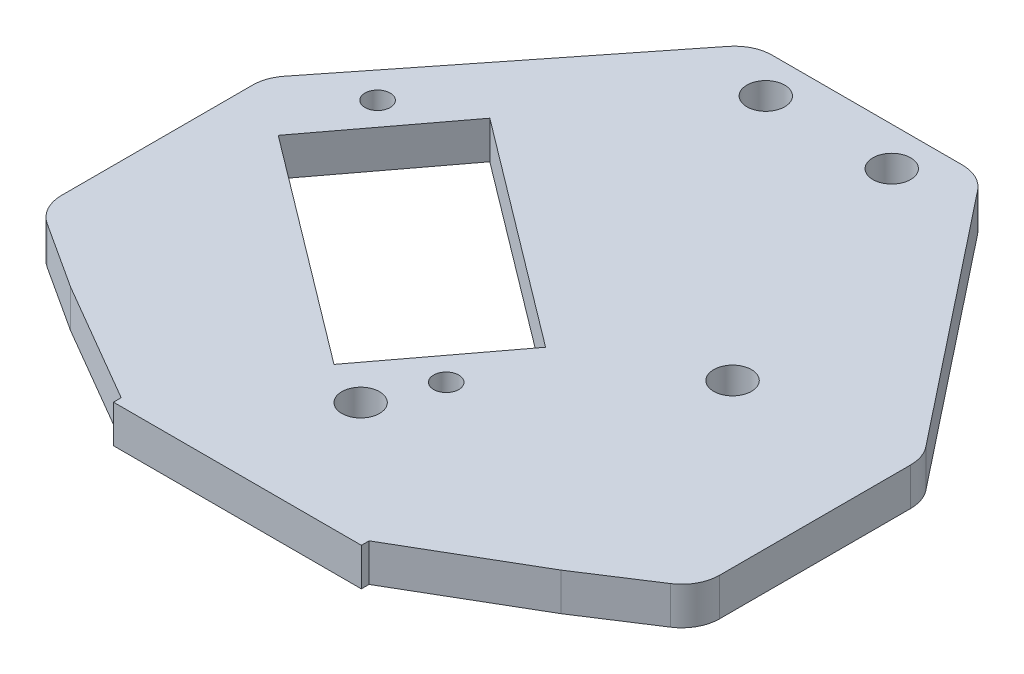
SolidWorks part; units mm, degrees
ref_plane "Front Plane" through (0, 0, 0) normal (0, 0, 1) x (1, 0, 0)
ref_plane "Top Plane" through (0, 0, 0) normal (0, 1, 0) x (1, 0, 0)
ref_plane "Right Plane" through (0, 0, 0) normal (1, 0, 0) x (0, 0, -1)
sketch "Sketch1" plane through (0, 0, 0) normal (0, 1, 0) x (1, 0, 0)
  line L7 (-4.1595, 37.5951) -> (4.1595, 37.5951)
  line L8 (-9.9025, 36.4566) -> (-20.3157, 23.2959) construction
  line L10 (0, 0) -> (0, -15.9475) construction
  line L12 (-9.9025, 36.4566) -> (-20.3157, 23.2959)
  line L15 (-20.9631, 21.4344) -> (-20.9631, -5.9026) construction
  line L16 (-19.4729, -6.2109) -> (-9.8452, -11.8182)
  line L19 (-9.8452, -11.8182) -> (-9.8452, -21.8182)
  line L21 (0, 43.4367) -> (0, 47.8638) construction
  line L22 (-9.8452, -21.8182) -> (-6.8452, -21.8182)
  line L23 (-6.8452, -21.8182) -> (-6.8452, -12.4305)
  line L24 (-6.8452, -12.4305) -> (6.8452, -12.4305)
  line L25 (-4.1595, 37.5951) -> (-7.5499, 37.5951)
  line L28 (24.762, -2.7815) -> (19.4729, -6.2109)
  line L29 (26.1299, 14.9044) -> (26.1299, -0.2643)
  line L30 (18.8536, 25.1438) -> (25.4825, 16.7659)
  line L31 (-18.8536, 25.1438) -> (-25.4825, 16.7659)
  line L32 (-26.1299, 14.9044) -> (-26.1299, -0.2643)
  line L33 (-24.762, -2.7815) -> (-19.4729, -6.2109)
  line L34 (4.1595, 37.5951) -> (7.5499, 37.5951)
  line L35 (6.8452, -21.8182) -> (6.8452, -12.4305)
  line L36 (9.8452, -21.8182) -> (6.8452, -21.8182)
  line L37 (9.8452, -11.8182) -> (9.8452, -21.8182)
  line L38 (19.4729, -6.2109) -> (9.8452, -11.8182)
  line L39 (0, 0) -> (0, 37.5951) construction
  line L42 (9.9025, 36.4566) -> (20.3157, 23.2959)
  arc A1 (-7.5499, 37.5951) -> (-9.9025, 36.4566) centre (-7.5499, 34.5951) ccw construction
  circle A4 centre (-5.0017, 34.5359) radius 1.5 construction
  circle A8 centre (-5.0017, 34.5359) radius 1.5
  arc A11 (-7.5499, 37.5951) -> (-9.9025, 36.4566) centre (-7.5499, 34.5951) ccw
  arc A12 (-19.7137, -6.0547) -> (-19.4729, -6.2109) centre (-17.9631, -3.6185) ccw
  arc A14 (25.4825, 16.7659) -> (26.1299, 14.9044) centre (23.1299, 14.9044) cw
  arc A15 (26.1299, -0.2643) -> (24.762, -2.7815) centre (23.1299, -0.2643) cw
  arc A16 (19.7137, -6.0547) -> (19.4729, -6.2109) centre (17.9631, -3.6185) cw
  arc A17 (-26.1299, -0.2643) -> (-24.762, -2.7815) centre (-23.1299, -0.2643) ccw
  arc A18 (-25.4825, 16.7659) -> (-26.1299, 14.9044) centre (-23.1299, 14.9044) ccw
  arc A19 (7.5499, 37.5951) -> (9.9025, 36.4566) centre (7.5499, 34.5951) cw
  circle A20 centre (5.0017, 34.5359) radius 1.5
  point P28 (0.1548, -12.4305)
  point P33 (-20.9631, -5.343)
  point P37 (0, -12.4305)
  point P41 (0.1548, -12.4305)
  point P46 (26.1299, 15.9477)
  point P48 (26.1299, -1.8946)
  point P49 (-0.1548, -12.4305)
  point P50 (20.9631, -5.343)
  point P54 (-26.1299, -1.8946)
  point P57 (-26.1299, 15.9477)
  dimension "D1" = 3
  dimension "D3" = 3
  dimension "D4" = 10
extrude "Boss-Extrude2" add sketch "Sketch1" along normal blind 3 contours A11 L12 A12 L16 L19 L22 L23 A8 region at (0, 0, -10.32)
mirror "Mirror1" about plane through (0, 0, 0) normal (1, 0, 0) of "Boss-Extrude2"
sketch "Sketch3" plane through (9.8452, 0, 0) normal (1, 0, 0) x (0, 0, -1)
  line L0 (0, 0) -> (-5.4214, -2.0662)
  line L1 (-10.362, -2.9757) -> (-38.362, -2.9757)
  line L2 (-46.7647, 6.1171) -> (-46.7647, 8.8248)
  line L3 (-36.7549, 18.9944) -> (-26.7549, 18.9944)
  line L4 (-14.3131, 13.6377) -> (-3.6185, 3)
  line L5 (-3.6185, 3) -> (0, 0)
  line L6 (-11.8182, 3) -> (-11.8182, 0) construction
  arc A0 (-5.4214, -2.0662) -> (-10.362, -2.9757) centre (-10.362, 10.8976) cw
  arc A1 (-38.362, -2.9757) -> (-43.5481, -1.0139) centre (-38.362, 4.8597) cw
  arc A2 (-43.5481, -1.0139) -> (-46.7647, 6.1171) centre (-37.2518, 6.1171) cw
  circle A5 centre (-29.5682, 8.0684) radius 5 construction
  arc A7 (-26.7549, 18.9944) -> (-14.3131, 13.6377) centre (-26.7549, 1.8671) cw
  arc A8 (-36.7549, 18.9944) -> (-46.7647, 8.8248) centre (-36.4897, 8.7223) ccw
  dimension "D1" = 10
  dimension "D2" = 17.75
  dimension "D3" = 28
  dimension "D4" = 10
extrude "Boss-Extrude3" add sketch "Sketch3" against normal blind 3
sketch "Sketch4" plane through (9.8452, 0, 0) normal (1, 0, 0) x (0, 0, -1)
  circle A0 centre (-29.5682, 8.0684) radius 5
mirror "Mirror2" about plane through (0, 0, 0) normal (1, 0, 0) of "Boss-Extrude3"
extrude "Cut-Extrude1" cut sketch "Sketch4" against normal up to surface (3 mm away) rebuild error yes
sketch "Sketch5" plane through (-9.8452, 0, 0) normal (-1, 0, 0) x (0, 0, 1)
  line L0 (14.3482, 8.0684) -> (44.7882, 8.0684) construction
  line L1 (14.3482, 8.5684) -> (44.7882, 8.5684)
  line L2 (14.3482, 7.5684) -> (44.7882, 7.5684)
  line L3 (29.5682, 1.2134) -> (29.5682, 14.9234) construction
  line L4 (29.0682, 1.2134) -> (29.0682, 14.9234)
  line L5 (30.0682, 1.2134) -> (30.0682, 14.9234)
  circle A0 centre (29.5682, 8.0684) radius 5 construction
  circle A1 centre (29.5682, 8.0684) radius 5 construction
  arc A2 (14.3482, 8.5684) -> (14.3482, 7.5684) centre (14.3482, 8.0684) ccw
  arc A3 (44.7882, 7.5684) -> (44.7882, 8.5684) centre (44.7882, 8.0684) ccw
  arc A4 (29.0682, 1.2134) -> (30.0682, 1.2134) centre (29.5682, 1.2134) ccw
  arc A5 (30.0682, 14.9234) -> (29.0682, 14.9234) centre (29.5682, 14.9234) ccw
  circle A6 centre (29.5682, 8.0684) radius 3.5
  point P5 (29.5682, 8.0684)
  point P11 (29.5682, 8.0684)
  dimension "D1" = 0.5
  dimension "D2" = 0.5
  dimension "D5" = 10
  dimension "D6" = 7
  dimension "D3" = 30.44
  dimension "D4" = 13.71
extrude "Cut-Extrude2" cut sketch "Sketch5" against normal blind 3 contours L5 A6 L2 | L2 A6 L4 | L4 A6 L1 | L1 A6 L5 | L2 A3 L1 A2 | L5 A4 L4 A5 region at (-9.8452, 9.7725, 27.8641) region at (-9.8452, 6.3644, 27.8641) region at (-9.8452, 9.7725, 31.2723) region at (-9.8452, 6.3644, 31.2723)
sketch "Sketch7" plane through (0, 3, 0) normal (0, 1, 0) x (1, 0, 0)
  line L0 (-14.4326, 22.0478) -> (3.5367, 8.507)
  line L1 (3.5367, 8.507) -> (-3.6851, -1.0766)
  line L2 (-3.6851, -1.0766) -> (-21.6544, 12.4642)
  line L3 (-21.6544, 12.4642) -> (-14.4326, 22.0478)
  line L26 (-6.8452, -3.6185) -> (-6.8452, -12.4305)
  line L27 (-6.8452, -3.6185) -> (-6.8452, -12.4305)
  line L42 (6.8452, -3.6185) -> (9.8452, -3.6185)
  line L43 (6.8452, -3.6185) -> (9.8452, -3.6185)
  line L44 (-9.9025, 36.4566) -> (-25.4825, 16.7659)
  line L45 (-9.9025, 36.4566) -> (-25.4825, 16.7659)
  line L46 (-19.4729, -6.2109) -> (-9.8452, -11.8182)
  line L47 (-19.4729, -6.2109) -> (-9.8452, -11.8182)
  line L48 (-9.8452, -11.8182) -> (-9.8452, -3.6185)
  line L50 (-9.8452, -11.8182) -> (-9.8452, -3.6185)
  line L52 (-24.762, -2.7815) -> (-19.4729, -6.2109)
  line L53 (-24.762, -2.7815) -> (-19.4729, -6.2109)
  line L54 (-9.8452, -3.6185) -> (-6.8452, -3.6185)
  line L55 (-9.8452, -3.6185) -> (-6.8452, -3.6185)
  line L56 (-26.1299, 14.9044) -> (-26.1299, -0.2643)
  line L57 (-26.1299, 14.9044) -> (-26.1299, -0.2643)
  line L62 (7.5499, 37.5951) -> (-7.5499, 37.5951)
  line L64 (7.5499, 37.5951) -> (-7.5499, 37.5951)
  line L66 (-6.8452, -12.4305) -> (6.8452, -12.4305)
  line L68 (-6.8452, -12.4305) -> (6.8452, -12.4305)
  line L70 (6.8452, -12.4305) -> (6.8452, -3.6185)
  line L72 (6.8452, -12.4305) -> (6.8452, -3.6185)
  line L74 (9.8452, -3.6185) -> (9.8452, -11.8182)
  line L76 (9.8452, -3.6185) -> (9.8452, -11.8182)
  line L78 (9.8452, -11.8182) -> (19.4729, -6.2109)
  line L80 (9.8452, -11.8182) -> (19.4729, -6.2109)
  line L82 (19.4729, -6.2109) -> (24.762, -2.7815)
  line L83 (19.4729, -6.2109) -> (24.762, -2.7815)
  line L84 (26.1299, -0.2643) -> (26.1299, 14.9044)
  line L85 (26.1299, -0.2643) -> (26.1299, 14.9044)
  line L86 (25.4825, 16.7659) -> (9.9025, 36.4566)
  line L87 (25.4825, 16.7659) -> (9.9025, 36.4566)
  circle A0 centre (-20.1199, 18.8207) radius 1
  circle A1 centre (2.0023, 2.1505) radius 1
  arc A3 (-7.5499, 37.5951) -> (-9.9025, 36.4566) centre (-7.5499, 34.5951) ccw
  arc A18 (-7.5499, 37.5951) -> (-9.9025, 36.4566) centre (-7.5499, 34.5951) ccw
  arc A19 (-25.4825, 16.7659) -> (-26.1299, 14.9044) centre (-23.1299, 14.9044) ccw
  arc A20 (-25.4825, 16.7659) -> (-26.1299, 14.9044) centre (-23.1299, 14.9044) ccw
  arc A22 (-26.1299, -0.2643) -> (-24.762, -2.7815) centre (-23.1299, -0.2643) ccw
  arc A24 (-26.1299, -0.2643) -> (-24.762, -2.7815) centre (-23.1299, -0.2643) ccw
  arc A25 (24.762, -2.7815) -> (26.1299, -0.2643) centre (23.1299, -0.2643) ccw
  arc A26 (24.762, -2.7815) -> (26.1299, -0.2643) centre (23.1299, -0.2643) ccw
  arc A27 (26.1299, 14.9044) -> (25.4825, 16.7659) centre (23.1299, 14.9044) ccw
  arc A28 (26.1299, 14.9044) -> (25.4825, 16.7659) centre (23.1299, 14.9044) ccw
  arc A29 (9.9025, 36.4566) -> (7.5499, 37.5951) centre (7.5499, 34.5951) ccw
  arc A30 (9.9025, 36.4566) -> (7.5499, 37.5951) centre (7.5499, 34.5951) ccw
  dimension "D2" = 12
  dimension "D3" = 22.5
  dimension "D1" = 0
sketch "Sketch8" plane through (0, 3, 0) normal (0, 1, 0) x (1, 0, 0)
  line L0 (-14.4326, 22.0478) -> (3.5367, 8.507) construction
  line L1 (3.5367, 8.507) -> (-3.6851, -1.0766) construction
  line L2 (-3.6851, -1.0766) -> (-21.6544, 12.4642) construction
  line L3 (-21.6544, 12.4642) -> (-14.4326, 22.0478) construction
  line L4 (-14.4326, 22.0478) -> (3.5367, 8.507)
  line L5 (3.5367, 8.507) -> (-3.6851, -1.0766)
  line L6 (-3.6851, -1.0766) -> (-21.6544, 12.4642)
  line L7 (-21.6544, 12.4642) -> (-14.4326, 22.0478)
  line L28 (-24.762, -2.7815) -> (-19.4729, -6.2109)
  line L30 (-6.8452, -3.6185) -> (-6.8452, -12.4305)
  line L31 (-6.8452, -3.6185) -> (-6.8452, -12.4305)
  line L44 (-24.762, -2.7815) -> (-19.4729, -6.2109)
  line L48 (6.8452, -3.6185) -> (9.8452, -3.6185)
  line L49 (6.8452, -3.6185) -> (9.8452, -3.6185)
  line L50 (-9.9025, 36.4566) -> (-25.4825, 16.7659)
  line L51 (-9.9025, 36.4566) -> (-25.4825, 16.7659)
  line L52 (-26.1299, 14.9044) -> (-26.1299, -0.2643)
  line L53 (-26.1299, 14.9044) -> (-26.1299, -0.2643)
  line L54 (-19.4729, -6.2109) -> (-9.8452, -11.8182)
  line L55 (-19.4729, -6.2109) -> (-9.8452, -11.8182)
  line L56 (-9.8452, -11.8182) -> (-9.8452, -3.6185)
  line L57 (-9.8452, -11.8182) -> (-9.8452, -3.6185)
  line L58 (-9.8452, -3.6185) -> (-6.8452, -3.6185)
  line L59 (-9.8452, -3.6185) -> (-6.8452, -3.6185)
  line L64 (7.5499, 37.5951) -> (-7.5499, 37.5951)
  line L66 (7.5499, 37.5951) -> (-7.5499, 37.5951)
  line L68 (-6.8452, -12.4305) -> (6.8452, -12.4305)
  line L70 (-6.8452, -12.4305) -> (6.8452, -12.4305)
  line L72 (6.8452, -12.4305) -> (6.8452, -3.6185)
  line L74 (6.8452, -12.4305) -> (6.8452, -3.6185)
  line L76 (9.8452, -3.6185) -> (9.8452, -11.8182)
  line L78 (9.8452, -3.6185) -> (9.8452, -11.8182)
  line L80 (9.8452, -11.8182) -> (19.4729, -6.2109)
  line L82 (9.8452, -11.8182) -> (19.4729, -6.2109)
  line L84 (19.4729, -6.2109) -> (24.762, -2.7815)
  line L85 (19.4729, -6.2109) -> (24.762, -2.7815)
  line L86 (26.1299, -0.2643) -> (26.1299, 14.9044)
  line L87 (26.1299, -0.2643) -> (26.1299, 14.9044)
  line L88 (25.4825, 16.7659) -> (9.9025, 36.4566)
  line L89 (25.4825, 16.7659) -> (9.9025, 36.4566)
  circle A0 centre (-20.1199, 18.8207) radius 1 construction
  circle A1 centre (2.0023, 2.1505) radius 1 construction
  circle A2 centre (-20.1199, 18.8207) radius 1
  circle A3 centre (2.0023, 2.1505) radius 1
  arc A5 (-7.5499, 37.5951) -> (-9.9025, 36.4566) centre (-7.5499, 34.5951) ccw
  arc A18 (-7.5499, 37.5951) -> (-9.9025, 36.4566) centre (-7.5499, 34.5951) ccw
  arc A19 (-25.4825, 16.7659) -> (-26.1299, 14.9044) centre (-23.1299, 14.9044) ccw
  arc A20 (-25.4825, 16.7659) -> (-26.1299, 14.9044) centre (-23.1299, 14.9044) ccw
  arc A21 (-26.1299, -0.2643) -> (-24.762, -2.7815) centre (-23.1299, -0.2643) ccw
  arc A22 (-26.1299, -0.2643) -> (-24.762, -2.7815) centre (-23.1299, -0.2643) ccw
  arc A23 (24.762, -2.7815) -> (26.1299, -0.2643) centre (23.1299, -0.2643) ccw
  arc A24 (24.762, -2.7815) -> (26.1299, -0.2643) centre (23.1299, -0.2643) ccw
  arc A25 (26.1299, 14.9044) -> (25.4825, 16.7659) centre (23.1299, 14.9044) ccw
  arc A26 (26.1299, 14.9044) -> (25.4825, 16.7659) centre (23.1299, 14.9044) ccw
  arc A27 (9.9025, 36.4566) -> (7.5499, 37.5951) centre (7.5499, 34.5951) ccw
  arc A28 (9.9025, 36.4566) -> (7.5499, 37.5951) centre (7.5499, 34.5951) ccw
  dimension "D1" = 0
sketch "Sketch9" plane through (0, 3, 0) normal (0, 1, 0) x (1, 0, 0)
  line L0 (3.5367, 8.507) -> (-3.6851, -1.0766) construction
  line L1 (-14.4326, 22.0478) -> (3.5367, 8.507) construction
  line L2 (-3.6851, -1.0766) -> (-21.6544, 12.4642) construction
  line L3 (-21.6544, 12.4642) -> (-14.4326, 22.0478) construction
  line L4 (3.5367, 8.507) -> (-3.6851, -1.0766)
  line L5 (-14.4326, 22.0478) -> (3.5367, 8.507)
  line L6 (-3.6851, -1.0766) -> (-21.6544, 12.4642)
  line L7 (-21.6544, 12.4642) -> (-14.4326, 22.0478)
  line L28 (-24.762, -2.7815) -> (-19.4729, -6.2109)
  line L30 (-6.8452, -3.6185) -> (-6.8452, -12.4305)
  line L31 (-6.8452, -3.6185) -> (-6.8452, -12.4305)
  line L44 (-24.762, -2.7815) -> (-19.4729, -6.2109)
  line L48 (6.8452, -3.6185) -> (9.8452, -3.6185)
  line L49 (6.8452, -3.6185) -> (9.8452, -3.6185)
  line L50 (-9.9025, 36.4566) -> (-25.4825, 16.7659)
  line L51 (-26.1299, 14.9044) -> (-26.1299, -0.2643)
  line L52 (-19.4729, -6.2109) -> (-9.8452, -11.8182)
  line L53 (-19.4729, -6.2109) -> (-9.8452, -11.8182)
  line L54 (-9.8452, -11.8182) -> (-9.8452, -3.6185)
  line L55 (-9.8452, -11.8182) -> (-9.8452, -3.6185)
  line L56 (-9.8452, -3.6185) -> (-6.8452, -3.6185)
  line L57 (-9.8452, -3.6185) -> (-6.8452, -3.6185)
  line L62 (7.5499, 37.5951) -> (-7.5499, 37.5951)
  line L63 (7.5499, 37.5951) -> (-7.5499, 37.5951)
  line L64 (-6.8452, -12.4305) -> (6.8452, -12.4305)
  line L65 (-6.8452, -12.4305) -> (6.8452, -12.4305)
  line L66 (6.8452, -12.4305) -> (6.8452, -3.6185)
  line L67 (6.8452, -12.4305) -> (6.8452, -3.6185)
  line L68 (9.8452, -3.6185) -> (9.8452, -11.8182)
  line L69 (9.8452, -3.6185) -> (9.8452, -11.8182)
  line L70 (9.8452, -11.8182) -> (19.4729, -6.2109)
  line L71 (9.8452, -11.8182) -> (19.4729, -6.2109)
  line L72 (19.4729, -6.2109) -> (24.762, -2.7815)
  line L73 (19.4729, -6.2109) -> (24.762, -2.7815)
  line L74 (26.1299, -0.2643) -> (26.1299, 14.9044)
  line L75 (26.1299, -0.2643) -> (26.1299, 14.9044)
  line L76 (25.4825, 16.7659) -> (9.9025, 36.4566)
  line L77 (25.4825, 16.7659) -> (9.9025, 36.4566)
  circle A0 centre (2.0023, 2.1505) radius 1 construction
  circle A1 centre (-20.1199, 18.8207) radius 1 construction
  circle A2 centre (2.0023, 2.1505) radius 1
  circle A4 centre (-20.1199, 18.8207) radius 1
  arc A6 (-7.5499, 37.5951) -> (-9.9025, 36.4566) centre (-7.5499, 34.5951) ccw
  arc A21 (-7.5499, 37.5951) -> (-9.9025, 36.4566) centre (-7.5499, 34.5951) ccw
  arc A22 (-25.4825, 16.7659) -> (-26.1299, 14.9044) centre (-23.1299, 14.9044) ccw
  arc A23 (-26.1299, -0.2643) -> (-24.762, -2.7815) centre (-23.1299, -0.2643) ccw
  arc A24 (-26.1299, -0.2643) -> (-24.762, -2.7815) centre (-23.1299, -0.2643) ccw
  arc A25 (24.762, -2.7815) -> (26.1299, -0.2643) centre (23.1299, -0.2643) ccw
  arc A26 (24.762, -2.7815) -> (26.1299, -0.2643) centre (23.1299, -0.2643) ccw
  arc A27 (26.1299, 14.9044) -> (25.4825, 16.7659) centre (23.1299, 14.9044) ccw
  arc A28 (26.1299, 14.9044) -> (25.4825, 16.7659) centre (23.1299, 14.9044) ccw
  arc A29 (9.9025, 36.4566) -> (7.5499, 37.5951) centre (7.5499, 34.5951) ccw
  arc A30 (9.9025, 36.4566) -> (7.5499, 37.5951) centre (7.5499, 34.5951) ccw
  dimension "D1" = 0
sketch "Sketch10" plane through (0, 3, 0) normal (0, 1, 0) x (1, 0, 0)
  line L16 (-6.8452, -3.6185) -> (-6.8452, -12.4305)
  line L17 (-6.8452, -12.4305) -> (6.8452, -12.4305)
  line L18 (6.8452, -12.4305) -> (6.8452, -3.6185)
  line L19 (6.8452, -3.6185) -> (9.8452, -3.6185)
  line L20 (9.8452, -3.6185) -> (9.8452, -11.8182)
  line L21 (9.8452, -11.8182) -> (19.4729, -6.2109)
  line L22 (19.4729, -6.2109) -> (24.762, -2.7815)
  line L23 (26.1299, -0.2643) -> (26.1299, 14.9044)
  line L24 (25.4825, 16.7659) -> (9.9025, 36.4566)
  line L25 (7.5499, 37.5951) -> (-7.5499, 37.5951)
  line L26 (-9.9025, 36.4566) -> (-25.4825, 16.7659)
  line L27 (-26.1299, 14.9044) -> (-26.1299, -0.2643)
  line L28 (-24.762, -2.7815) -> (-19.4729, -6.2109)
  line L29 (-19.4729, -6.2109) -> (-9.8452, -11.8182)
  line L30 (-9.8452, -11.8182) -> (-9.8452, -3.6185)
  line L31 (-9.8452, -3.6185) -> (-6.8452, -3.6185)
  line L32 (-6.8452, -3.6185) -> (-6.8452, -12.4305)
  line L33 (-6.8452, -12.4305) -> (6.8452, -12.4305)
  line L34 (6.8452, -12.4305) -> (6.8452, -3.6185)
  line L35 (6.8452, -3.6185) -> (9.8452, -3.6185)
  line L36 (9.8452, -3.6185) -> (9.8452, -11.8182)
  line L37 (9.8452, -11.8182) -> (19.4729, -6.2109)
  line L38 (19.4729, -6.2109) -> (24.762, -2.7815)
  line L39 (26.1299, -0.2643) -> (26.1299, 14.9044)
  line L40 (25.4825, 16.7659) -> (9.9025, 36.4566)
  line L41 (7.5499, 37.5951) -> (-7.5499, 37.5951)
  line L42 (-9.9025, 36.4566) -> (-25.4825, 16.7659)
  line L43 (-26.1299, 14.9044) -> (-26.1299, -0.2643)
  line L44 (-24.762, -2.7815) -> (-19.4729, -6.2109)
  line L45 (-19.4729, -6.2109) -> (-9.8452, -11.8182)
  line L46 (-9.8452, -11.8182) -> (-9.8452, -3.6185)
  line L47 (-9.8452, -3.6185) -> (-6.8452, -3.6185)
  arc A6 (24.762, -2.7815) -> (26.1299, -0.2643) centre (23.1299, -0.2643) ccw
  arc A7 (26.1299, 14.9044) -> (25.4825, 16.7659) centre (23.1299, 14.9044) ccw
  arc A8 (9.9025, 36.4566) -> (7.5499, 37.5951) centre (7.5499, 34.5951) ccw
  arc A9 (-7.5499, 37.5951) -> (-9.9025, 36.4566) centre (-7.5499, 34.5951) ccw
  arc A10 (-25.4825, 16.7659) -> (-26.1299, 14.9044) centre (-23.1299, 14.9044) ccw
  arc A11 (-26.1299, -0.2643) -> (-24.762, -2.7815) centre (-23.1299, -0.2643) ccw
  arc A12 (24.762, -2.7815) -> (26.1299, -0.2643) centre (23.1299, -0.2643) ccw
  arc A13 (26.1299, 14.9044) -> (25.4825, 16.7659) centre (23.1299, 14.9044) ccw
  arc A14 (9.9025, 36.4566) -> (7.5499, 37.5951) centre (7.5499, 34.5951) ccw
  arc A15 (-7.5499, 37.5951) -> (-9.9025, 36.4566) centre (-7.5499, 34.5951) ccw
  arc A16 (-25.4825, 16.7659) -> (-26.1299, 14.9044) centre (-23.1299, 14.9044) ccw
  arc A17 (-26.1299, -0.2643) -> (-24.762, -2.7815) centre (-23.1299, -0.2643) ccw
  dimension "D1" = 0
extrude "Cut-Extrude3" cut sketch "Sketch9" against normal blind 10 contours L7 L6 L4 L5 | A4 | A2 region at (-9.0588, 3, -10.4856) region at (2.0023, 3, -2.1505) region at (-20.1199, 3, -18.8207)
sketch "Sketch16" plane through (0, 3, 0) normal (0, 1, 0) x (1, 0, 0)
  circle A0 centre (13.2517, 13.6459) radius 1.5
  circle A1 centre (5.0017, 34.5359) radius 1.5 construction
  dimension "D1" = 3
  dimension "D2" = 20.89
  dimension "D3" = 8.25
extrude "Cut-Extrude4" cut sketch "Sketch16" against normal blind 10
sketch "Sketch18" plane through (6.8452, 0, 0) normal (-1, 0, 0) x (0, 0, 1)
  circle A0 centre (29.5682, 8.0684) radius 3.5
  dimension "D1" = 7
sketch "Sketch19" plane through (0, 3, 0) normal (0, 1, 0) x (1, 0, 0)
  circle A0 centre (0, -2.643) radius 1.5
  dimension "D1" = 3
extrude "Cut-Extrude6" cut sketch "Sketch19" against normal blind 10
extrude "Boss-Extrude4" add sketch "Sketch18" against normal blind 20
sketch "Sketch20" plane through (26.8452, 0, 0) normal (1, 0, 0) x (0, 0, -1)
  circle A0 centre (-29.5682, 8.0684) radius 1.5
  dimension "D1" = 3
extrude "Cut-Extrude7" cut sketch "Sketch20" against normal blind 12
sketch "Sketch21" plane through (0, 0, -37.5951) normal (0, 0, -1) x (-1, 0, 0)
  line L1 (9.8452, 3) -> (-29.5048, 3)
  line L2 (9.8452, 3) -> (9.8452, 20.9541)
  line L3 (9.8452, 20.9541) -> (-29.5048, 20.9541)
  line L4 (-29.5048, 3) -> (-29.5048, 20.9541)
  line L5 (-9.9025, 0) -> (9.9025, 0)
  line L6 (-9.9025, 0) -> (-9.9025, -5.4498)
  line L7 (-9.9025, -5.4498) -> (9.9025, -5.4498)
  line L8 (9.9025, 0) -> (9.9025, -5.4498)
extrude "Cut-Extrude8" cut sketch "Sketch21" against normal through all both
sketch "Sketch22" plane through (0, 3, 0) normal (0, 1, 0) x (1, 0, 0)
  line L1 (6.8452, -12.4305) -> (11.0161, -12.4305)
  line L2 (6.8452, -12.4305) -> (6.8452, -47.7666)
  line L3 (6.8452, -47.7666) -> (11.0161, -47.7666)
  line L4 (11.0161, -12.4305) -> (11.0161, -47.7666)
  line L5 (-6.8452, -12.4305) -> (-11.7484, -12.4305)
  line L6 (-6.8452, -12.4305) -> (-6.8452, -49.1421)
  line L7 (-6.8452, -49.1421) -> (-11.7484, -49.1421)
  line L8 (-11.7484, -12.4305) -> (-11.7484, -49.1421)
extrude "Cut-Extrude9" cut sketch "Sketch22" against normal through all both
